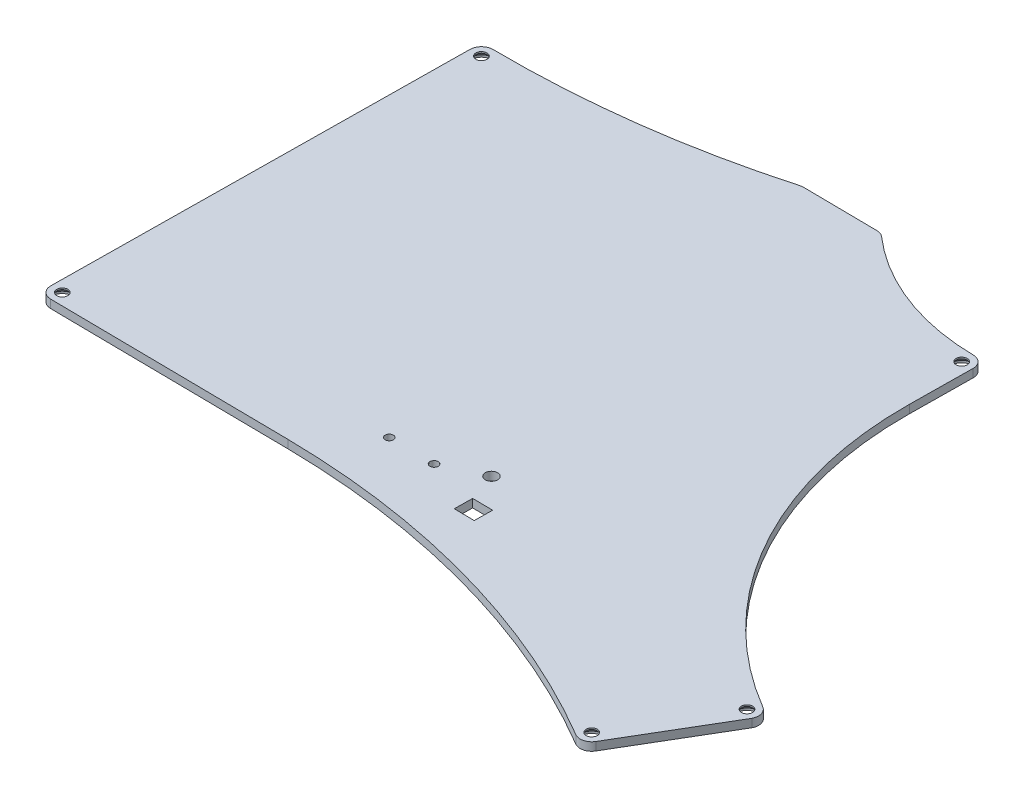
SolidWorks part; units mm, degrees
ref_plane "Front Plane" through (0, 0, 0) normal (0, 0, 1) x (1, 0, 0)
ref_plane "Top Plane" through (0, 0, 0) normal (0, 1, 0) x (1, 0, 0)
ref_plane "Right Plane" through (0, 0, 0) normal (1, 0, 0) x (0, 0, -1)
sketch "Main" plane through (0, 0, 0) normal (0, 1, 0) x (1, 0, 0)
  line L13 (-13.8307, -87.7787) -> (-9.531, -87.8292) construction
  line L18 (-14.1284, -87.5752) -> (-9.2287, -87.6327) construction
  line L19 (-14.1284, -87.5752) -> (-14.18, -91.9749) construction
  line L20 (-9.2287, -87.6327) -> (-9.2803, -92.0324) construction
  line L21 (-14.18, -91.9749) -> (-9.2803, -92.0324) construction
  line L22 (-13.9765, -91.6773) -> (-13.9319, -87.8776) construction
  line L23 (-9.4322, -87.9303) -> (-9.4768, -91.7301) construction
  line L26 (-9.578, -91.8289) -> (-13.8777, -91.7785) construction
  line L69 (-108.9821, 6.4438) -> (-110.1609, -94.0493)
  line L70 (-21.3415, 17.9166) -> (-39.3403, 18.1277)
  line L71 (19.277, -14.8479) -> (19.4562, 0.4369)
  line L72 (52.0453, -123.8081) -> (66.1172, -99.9838)
  line L73 (-107.1963, -97.0843) -> (-48.9877, -97.7671)
  line L74 (-108.9821, 6.4438) -> (-110.1609, -94.0493) construction
  line L75 (-21.3415, 17.9166) -> (-39.3403, 18.1277) construction
  line L76 (19.277, -14.8479) -> (19.4562, 0.4369) construction
  line L77 (52.0453, -123.8081) -> (66.1172, -99.9838) construction
  line L78 (-107.1963, -97.0843) -> (-48.9877, -97.7671) construction
  circle A0 centre (-107.1611, -94.0845) radius 1.35 construction
  circle A1 centre (-105.9823, 6.4086) radius 1.35 construction
  circle A2 centre (16.4564, 0.4721) radius 1.35 construction
  circle A3 centre (63.4478, -98.6043) radius 1.35 construction
  circle A4 centre (49.4623, -122.2824) radius 1.35 construction
  circle A11 centre (-16.4973, -80.647) radius 1.5 construction
  circle A19 centre (-16.4973, -80.647) radius 1.5 construction
  circle A83 centre (-105.9823, 6.4086) radius 1.35 construction
  circle A84 centre (16.4564, 0.4721) radius 1.35 construction
  circle A85 centre (63.4478, -98.6043) radius 1.35 construction
  circle A86 centre (49.4623, -122.2824) radius 1.35 construction
  circle A87 centre (-107.1611, -94.0845) radius 1.35 construction
  circle A125 centre (-26.0492, -85.0152) radius 1 construction
  circle A126 centre (-37.0484, -84.8862) radius 1 construction
  arc A135 (-110.1609, -94.0493) -> (-107.1963, -97.0843) centre (-107.1611, -94.0845) ccw
  arc A136 (-105.9472, 9.4084) -> (-108.9821, 6.4438) centre (-105.9823, 6.4086) ccw
  arc A137 (-105.9472, 9.4084) -> (-40.1817, 18.0176) centre (-103.1967, 243.8923) ccw
  arc A138 (-39.3403, 18.1277) -> (-40.1817, 18.0176) centre (-39.3755, 15.128) ccw
  arc A139 (-19.4037, 17.1768) -> (-21.3415, 17.9166) centre (-21.3767, 14.9168) ccw
  arc A140 (-19.4037, 17.1768) -> (16.4916, 3.4719) centre (17.1434, 59.0395) ccw
  arc A141 (19.4562, 0.4369) -> (16.4916, 3.4719) centre (16.4564, 0.4721) ccw
  arc A142 (19.277, -14.8479) -> (64.9759, -96.0171) centre (112.2741, -15.9387) ccw
  arc A143 (66.1172, -99.9838) -> (64.9759, -96.0171) centre (63.4478, -98.6043) ccw
  arc A144 (47.9366, -124.8655) -> (52.0453, -123.8081) centre (49.4623, -122.2824) ccw
  arc A145 (47.9366, -124.8655) -> (-48.9877, -97.7671) centre (-51.2758, -292.8371) ccw
  arc A146 (-110.1609, -94.0493) -> (-107.1963, -97.0843) centre (-107.1611, -94.0845) ccw construction
  arc A147 (-105.9472, 9.4084) -> (-108.9821, 6.4438) centre (-105.9823, 6.4086) ccw construction
  arc A148 (-105.9472, 9.4084) -> (-40.1817, 18.0176) centre (-103.1967, 243.8923) ccw construction
  arc A149 (-39.3403, 18.1277) -> (-40.1817, 18.0176) centre (-39.3755, 15.128) ccw construction
  arc A150 (-19.4037, 17.1768) -> (-21.3415, 17.9166) centre (-21.3767, 14.9168) ccw construction
  arc A151 (-19.4037, 17.1768) -> (16.4916, 3.4719) centre (17.1434, 59.0395) ccw construction
  arc A152 (19.4562, 0.4369) -> (16.4916, 3.4719) centre (16.4564, 0.4721) ccw construction
  arc A153 (19.277, -14.8479) -> (64.9759, -96.0171) centre (112.2741, -15.9387) ccw construction
  arc A154 (66.1172, -99.9838) -> (64.9759, -96.0171) centre (63.4478, -98.6043) ccw construction
  arc A155 (47.9366, -124.8655) -> (52.0453, -123.8081) centre (49.4623, -122.2824) ccw construction
  arc A156 (47.9366, -124.8655) -> (-48.9877, -97.7671) centre (-51.2758, -292.8371) ccw construction
  dimension "D2" = 3
  dimension "D3" = 2
  dimension "D4" = 0.2
  dimension "D5" = 0.2
  dimension "D6" = 0.2
  dimension "D7" = 0.2
  dimension "D1" = 0
sketch "Sketch7" plane through (0, 0, 0) normal (0, 1, 0) x (1, 0, 0)
  line L0 (-14.1284, -87.5752) -> (-9.2287, -87.6327)
  line L1 (-9.2287, -87.6327) -> (-9.2803, -92.0324)
  line L2 (-9.2803, -92.0324) -> (-14.18, -91.9749)
  line L3 (-14.18, -91.9749) -> (-14.1284, -87.5752)
  line L42 (-108.7822, 6.4414) -> (-109.9609, -94.0516)
  line L43 (-107.194, -96.8843) -> (-48.9853, -97.5671)
  line L44 (51.8731, -123.7064) -> (65.942, -99.887)
  line L45 (19.077, -14.8455) -> (19.2563, 0.4392)
  line L46 (-21.3439, 17.7166) -> (-39.3427, 17.9278)
  line L47 (-108.7822, 6.4414) -> (-109.9609, -94.0516)
  line L48 (-107.194, -96.8843) -> (-48.9853, -97.5671)
  line L49 (51.8731, -123.7064) -> (65.942, -99.887)
  line L50 (19.077, -14.8455) -> (19.2563, 0.4392)
  line L51 (-21.3439, 17.7166) -> (-39.3427, 17.9278)
  circle A0 centre (-37.0484, -84.8862) radius 1
  circle A1 centre (-26.0492, -85.0152) radius 1
  circle A2 centre (-16.4973, -80.647) radius 1.5
  circle A3 centre (-37.0484, -84.8862) radius 1 construction
  circle A4 centre (-16.4973, -80.647) radius 1.5 construction
  circle A99 centre (-105.9823, 6.4086) radius 1.35
  circle A100 centre (16.4564, 0.4721) radius 1.35
  circle A101 centre (63.4478, -98.6043) radius 1.35
  circle A102 centre (49.4623, -122.2824) radius 1.35
  circle A103 centre (-107.1611, -94.0845) radius 1.35
  circle A104 centre (-107.1611, -94.0845) radius 1.35 construction
  arc A110 (-105.9495, 9.2084) -> (-108.7822, 6.4414) centre (-105.9823, 6.4086) ccw
  arc A111 (-109.9609, -94.0516) -> (-107.194, -96.8843) centre (-107.1611, -94.0845) ccw
  arc A112 (48.0383, -124.6933) -> (-48.9853, -97.5671) centre (-51.2758, -292.8371) ccw
  arc A113 (48.0383, -124.6933) -> (51.8731, -123.7064) centre (49.4623, -122.2824) ccw
  arc A114 (65.942, -99.887) -> (64.8742, -96.1893) centre (63.4478, -98.6043) ccw
  arc A115 (19.077, -14.8455) -> (64.8742, -96.1893) centre (112.2741, -15.9387) ccw
  arc A116 (19.2563, 0.4392) -> (16.4893, 3.2719) centre (16.4564, 0.4721) ccw
  arc A117 (-19.5353, 17.0261) -> (16.4893, 3.2719) centre (17.1434, 59.0395) ccw
  arc A118 (-19.5353, 17.0261) -> (-21.3439, 17.7166) centre (-21.3767, 14.9168) ccw
  arc A119 (-39.3427, 17.9278) -> (-40.1279, 17.825) centre (-39.3755, 15.128) ccw
  arc A120 (-105.9495, 9.2084) -> (-40.1279, 17.825) centre (-103.1967, 243.8923) ccw
  arc A121 (-105.9495, 9.2084) -> (-108.7822, 6.4414) centre (-105.9823, 6.4086) ccw
  arc A122 (-109.9609, -94.0516) -> (-107.194, -96.8843) centre (-107.1611, -94.0845) ccw
  arc A123 (48.0383, -124.6933) -> (-48.9853, -97.5671) centre (-51.2758, -292.8371) ccw
  arc A124 (48.0383, -124.6933) -> (51.8731, -123.7064) centre (49.4623, -122.2824) ccw
  arc A125 (65.942, -99.887) -> (64.8742, -96.1893) centre (63.4478, -98.6043) ccw
  arc A126 (19.077, -14.8455) -> (64.8742, -96.1893) centre (112.2741, -15.9387) ccw
  arc A127 (19.2563, 0.4392) -> (16.4893, 3.2719) centre (16.4564, 0.4721) ccw
  arc A128 (-19.5353, 17.0261) -> (16.4893, 3.2719) centre (17.1434, 59.0395) ccw
  arc A129 (-19.5353, 17.0261) -> (-21.3439, 17.7166) centre (-21.3767, 14.9168) ccw
  arc A130 (-39.3427, 17.9278) -> (-40.1279, 17.825) centre (-39.3755, 15.128) ccw
  arc A131 (-105.9495, 9.2084) -> (-40.1279, 17.825) centre (-103.1967, 243.8923) ccw
  dimension "D1" = 0.2
extrude "Main_plate" add sketch "Sketch7" against normal blind 2
sketch "Sketch8" plane through (0, -2, 0) normal (0, 1, 0) x (1, 0, 0)
  circle A0 centre (-105.9823, 6.4086) radius 2.5
  circle A1 centre (16.4564, 0.4721) radius 2.5
  circle A2 centre (63.4478, -98.6043) radius 2.5
  circle A3 centre (49.4623, -122.2824) radius 2.5
  circle A4 centre (-107.1611, -94.0845) radius 2.5
  dimension "D1" = 5
extrude "Screw_holes" cut sketch "Sketch8" along normal blind 1.7
chamfer "Chamfer1" distance 1.2 angle 45 5 edges at (-107.1611, -0.3, 96.5845) (49.4623, -0.3, 124.7824) (63.4478, -0.3, 101.1043) (16.4564, -0.3, 2.0279) (-105.9823, -0.3, -3.9086)
